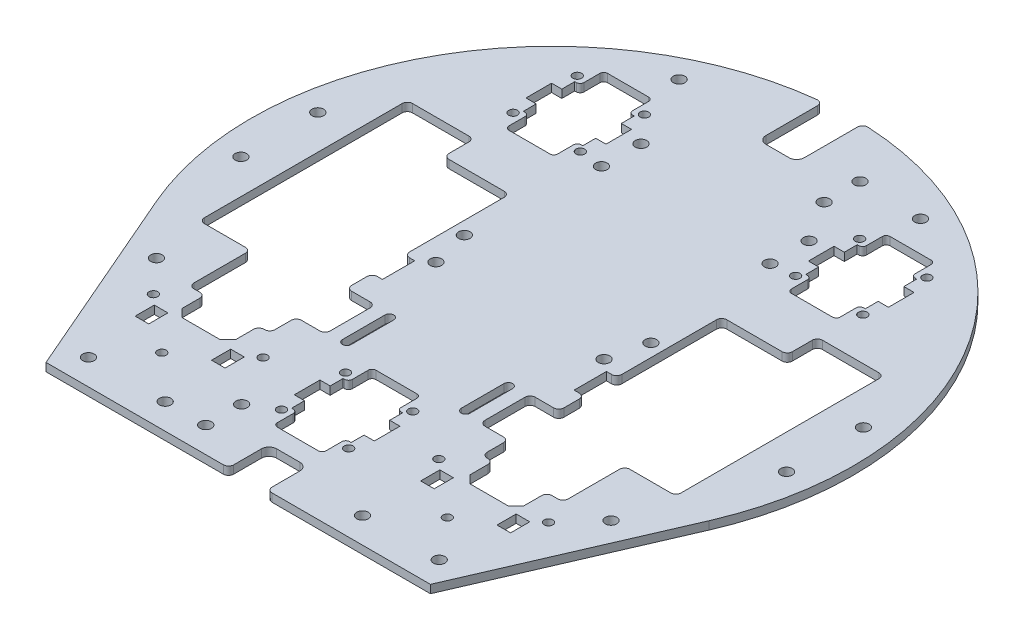
SolidWorks part; units mm, degrees
ref_plane "Front Plane" through (0, 0, 0) normal (0, 0, 1) x (1, 0, 0)
ref_plane "Top Plane" through (0, 0, 0) normal (0, 1, 0) x (1, 0, 0)
ref_plane "Right Plane" through (0, 0, 0) normal (1, 0, 0) x (0, 0, -1)
sketch "Sketch1" plane through (0, 0, 0) normal (0, 1, 0) x (1, 0, 0)
  circle A0 centre (0, 0) radius 117.5
  dimension "D1" = 235
extrude "Boss-Extrude1" add sketch "Sketch1" along normal blind 3.175
sketch "Sketch3" plane through (0, 0, 0) normal (0, 1, 0) x (1, 0, 0)
  line L3 (-107.8261, -46.6881) -> (-75, -122.5)
  line L5 (-75, -122.5) -> (75, -122.5)
  line L6 (75, -122.5) -> (107.8261, -46.6881)
  line L7 (107.8261, -46.6881) -> (-107.8261, -46.6881)
  line L8 (0, -122.5) -> (0, -117.5) construction
  circle A2 centre (0, 0) radius 117.5 construction
  dimension "D1" = 150
  dimension "D2" = 5
extrude "Boss-Extrude2" add sketch "Sketch3" along normal up to surface (3.175 mm away) up to face at (0, 3.175, 117.5)
sketch "Sketch4" plane through (0, 3.175, 0) normal (0, 1, 0) x (1, 0, 0)
  line L0 (70, 31.499) -> (70, -36.6986)
  line L1 (90, 31.499) -> (90, -36.6986)
  line L4 (93, 36.499) -> (67, 36.499)
  line L5 (90, -36.6986) -> (70, -36.6986) construction
  line L6 (67, 36.499) -> (67, 24.7405)
  line L7 (70, 31.499) -> (90, 31.499)
  line L8 (67, 24.7405) -> (41.4, 24.7405)
  line L9 (41.4, 24.7405) -> (41.4, -68.7747)
  line L10 (41.4, -68.7747) -> (73, -68.7747)
  line L11 (73, -68.7747) -> (73, -44.6986)
  line L12 (73, -44.6986) -> (93, -44.6986)
  line L13 (93, -44.6986) -> (93, 36.499)
  line L14 (46.4, 31.499) -> (89.2885, 31.499) construction
  line L15 (70, 31.499) -> (90, 31.499) construction
  line L19 (90, 31.499) -> (90, -36.6986) construction
  line L20 (70, 31.499) -> (70, -36.6986) construction
  line L22 (33.2, -41.8146) -> (33.2, -55.4255)
  line L24 (43.4, -41.8146) -> (33.2, -41.8146)
  line L25 (0, 0) -> (0, 30.6953) construction
  line L26 (-93, -44.6986) -> (-93, 36.499)
  line L27 (-73, -44.6986) -> (-93, -44.6986)
  line L28 (-73, -68.7747) -> (-73, -44.6986)
  line L29 (-41.4, -68.7747) -> (-73, -68.7747)
  line L30 (-41.4, 24.7405) -> (-41.4, -68.7747)
  line L31 (-67, 24.7405) -> (-41.4, 24.7405)
  line L32 (-67, 36.499) -> (-67, 24.7405)
  line L33 (-93, 36.499) -> (-67, 36.499)
  line L35 (33.2, -55.4255) -> (43.4, -55.4255) construction
  line L36 (39.4, -26.8239) -> (39.4, -18.2172)
  line L37 (39.4, -26.8239) -> (43.4, -26.8239)
  line L38 (43.4, -18.2172) -> (39.4, -18.2172)
  line L39 (68, 19.7405) -> (68, -67.7747)
  line L40 (68, -67.7747) -> (43.4, -67.7747)
  line L41 (43.4, 19.7405) -> (68, 19.7405)
  line L42 (43.4, 19.7405) -> (43.4, -18.2172)
  line L43 (43.4, -26.8239) -> (43.4, -41.8146)
  line L44 (43.4, -55.4255) -> (43.4, -67.7747)
  line L45 (43.4, -55.4255) -> (43.4, -67.7747) construction
  line L46 (43.4, -26.8239) -> (43.4, -41.8146) construction
  line L47 (43.4, 19.7405) -> (43.4, -18.2172) construction
  line L48 (43.4, 19.7405) -> (68, 19.7405) construction
  line L49 (68, -67.7747) -> (43.4, -67.7747) construction
  line L50 (68, 19.7405) -> (68, -67.7747) construction
  line L51 (43.4, -18.2172) -> (39.4, -18.2172) construction
  line L52 (39.4, -26.8239) -> (43.4, -26.8239) construction
  line L53 (39.4, -26.8239) -> (39.4, -18.2172) construction
  line L55 (43.4, -41.8146) -> (33.2, -41.8146) construction
  line L56 (33.2, -41.8146) -> (33.2, -55.4255) construction
  line L60 (33.2, -55.4255) -> (43.4, -55.4255)
  line L64 (90, -36.6986) -> (70, -36.6986)
  dimension "D1" = 2
  dimension "D2" = 5
  dimension "D3" = 5
  dimension "D4" = 8
  dimension "D5" = 3
  dimension "D6" = 5
  dimension "D7" = 5
  dimension "D8" = 3
  dimension "D9" = 2
extrude "Cut-Extrude1" cut sketch "Sketch4" against normal through all
sketch "Sketch8" plane through (0, 0, 0) normal (0, -1, 0) x (1, 0, 0)
  line L0 (-42, -78) -> (-68.225, -78) construction
  line L1 (13.1125, 12.5) -> (-13.1125, 12.5)
  line L2 (13.1125, 12.5) -> (13.1125, -12.5)
  line L3 (13.1125, -12.5) -> (-13.1125, -12.5)
  line L4 (-13.1125, 12.5) -> (-13.1125, -12.5)
  line L5 (13.1125, 12.5) -> (-13.1125, -12.5) construction
  line L6 (13.1125, -12.5) -> (-13.1125, 12.5) construction
  line L7 (-42, -53) -> (-42, -78) construction
  line L13 (0, 0) -> (0, -77.7063) construction
  line L14 (0, 80) -> (0, 0) construction
  line L15 (-42, -53) -> (-68.225, -53)
  line L16 (-42, -53) -> (-42, -78)
  line L17 (-42, -78) -> (-68.225, -78)
  line L18 (-68.225, -53) -> (-68.225, -78)
  line L19 (-42, -53) -> (-68.225, -78) construction
  line L20 (-42, -78) -> (-68.225, -53) construction
  line L21 (13.1125, 92.5) -> (-13.1125, 92.5)
  line L22 (13.1125, 92.5) -> (13.1125, 67.5)
  line L23 (13.1125, 67.5) -> (-13.1125, 67.5)
  line L24 (-13.1125, 92.5) -> (-13.1125, 67.5)
  line L25 (13.1125, 92.5) -> (-13.1125, 67.5) construction
  line L26 (13.1125, 67.5) -> (-13.1125, 92.5) construction
  line L27 (-42, -53) -> (-68.225, -53) construction
  line L28 (42, -78) -> (68.225, -78)
  line L29 (68.225, -53) -> (68.225, -78)
  line L30 (42, -78) -> (68.225, -53) construction
  line L31 (42, -53) -> (68.225, -78) construction
  line L32 (42, -53) -> (68.225, -53)
  line L33 (42, -53) -> (42, -78)
  point P0 (0, 0)
  point P15 (-55.1125, -65.5)
  point P20 (0, 80)
  point P29 (55.1125, -65.5)
  dimension "D1" = 42
  dimension "D2" = 80
hole_wizard "M3 Clearance Hole1" positions "Sketch9" profile "Sketch10" hole size "M3" standard "ANSI Metric" end condition through all
sketch "Sketch9" plane through (0, 3.175, 0) normal (0, 1, 0) x (1, 0, 0)
  point P0 (-68.225, 78)
  point P3 (-68.225, 53)
  point P6 (-42, 53)
  point P9 (-42, 78)
  point P12 (42, 78)
  point P15 (68.225, 78)
  point P18 (68.225, 53)
  point P21 (42, 53)
  point P24 (-13.1125, -67.5)
  point P27 (13.1125, -67.5)
  point P30 (13.1125, -92.5)
  point P33 (-13.1125, -92.5)
sketch "Sketch10" plane through (-68.225, 3.175, -78) normal (1, 0, 0) x (0, 0, 1)
  line L0 (0, 0) -> (0, 3.175)
  line L1 (0, 3.175) -> (1.7, 3.175)
  line L2 (1.7, 3.175) -> (1.7, 0)
  line L5 (1.7, 0) -> (0, 0)
  line L11 (0, -6.35) -> (0, 107.95) construction
  dimension "Thru Hole Dia." = 3.4
  dimension "Thru Hole Depth" = 3.175
sketch "Sketch11" plane through (0, 0, 0) normal (0, -1, 0) x (1, 0, 0)
  line L0 (47.6125, -48.2591) -> (62.6125, -48.2591)
  line L1 (62.6125, -82.7409) -> (47.6125, -82.7409)
  line L2 (62.6125, -82.7409) -> (47.6125, -82.7409)
  line L3 (47.6125, -48.2591) -> (62.6125, -48.2591)
  line L4 (-62.6125, -48.2591) -> (-47.6125, -48.2591)
  line L5 (-47.6125, -82.7409) -> (-62.6125, -82.7409)
  line L6 (-47.6125, -82.7409) -> (-62.6125, -82.7409)
  line L7 (-62.6125, -48.2591) -> (-47.6125, -48.2591)
  line L8 (-7.5, 97.2409) -> (7.5, 97.2409)
  line L9 (7.5, 62.7591) -> (-7.5, 62.7591)
  line L10 (7.5, 62.7591) -> (-7.5, 62.7591)
  line L11 (-7.5, 97.2409) -> (7.5, 97.2409)
sketch "Sketch12" plane through (0, 3.175, 0) normal (0, 1, 0) x (1, 0, 0)
  line L1 (-62.6125, 48.2591) -> (-47.6125, 48.2591) construction
  line L2 (-62.6125, 48.2591) -> (-62.6125, 82.7409) construction
  line L3 (-62.6125, 82.7409) -> (-47.6125, 82.7409) construction
  line L4 (-47.6125, 48.2591) -> (-47.6125, 82.7409) construction
  line L5 (47.6125, 48.2591) -> (62.6125, 48.2591) construction
  line L6 (47.6125, 48.2591) -> (47.6125, 82.7409) construction
  line L7 (47.6125, 82.7409) -> (62.6125, 82.7409) construction
  line L8 (62.6125, 48.2591) -> (62.6125, 82.7409) construction
  line L9 (-64.6125, 46.2591) -> (-45.6125, 46.2591)
  line L10 (-7.5, -97.2409) -> (7.5, -97.2409) construction
  line L11 (-7.5, -97.2409) -> (-7.5, -62.7591) construction
  line L12 (-7.5, -62.7591) -> (7.5, -62.7591) construction
  line L13 (7.5, -97.2409) -> (7.5, -62.7591) construction
  line L14 (-45.6125, 46.2591) -> (-45.6125, 84.7409)
  line L15 (-64.6125, 84.7409) -> (-45.6125, 84.7409)
  line L16 (-64.6125, 46.2591) -> (-64.6125, 84.7409)
  line L17 (45.6125, 46.2591) -> (64.6125, 46.2591)
  line L18 (64.6125, 46.2591) -> (64.6125, 84.7409)
  line L19 (45.6125, 84.7409) -> (64.6125, 84.7409)
  line L20 (45.6125, 46.2591) -> (45.6125, 84.7409)
  line L21 (-9.5, -99.2409) -> (9.5, -99.2409)
  line L22 (9.5, -99.2409) -> (9.5, -60.7591)
  line L23 (-9.5, -60.7591) -> (9.5, -60.7591)
  line L24 (-9.5, -99.2409) -> (-9.5, -60.7591)
  dimension "D1" = 2
extrude "Cut-Extrude3" cut sketch "Sketch12" against normal through all
sketch "Sketch13" plane through (0, 0, 0) normal (0, -1, 0) x (1, 0, 0)
  line L0 (-66.225, -75.0394) -> (-63.6125, -75.0394)
  line L1 (-63.6125, -55.9606) -> (-66.225, -55.9606)
  line L2 (-63.6125, -55.9606) -> (-66.225, -55.9606)
  line L3 (-66.225, -75.0394) -> (-63.6125, -75.0394)
  line L4 (-46.6125, -75.0394) -> (-44, -75.0394)
  line L5 (-44, -55.9606) -> (-46.6125, -55.9606)
  line L6 (-44, -55.9606) -> (-46.6125, -55.9606)
  line L7 (-46.6125, -75.0394) -> (-44, -75.0394)
  line L8 (63.6125, -75.0394) -> (66.225, -75.0394)
  line L9 (66.225, -55.9606) -> (63.6125, -55.9606)
  line L10 (66.225, -55.9606) -> (63.6125, -55.9606)
  line L11 (63.6125, -75.0394) -> (66.225, -75.0394)
  line L12 (44, -75.0394) -> (46.6125, -75.0394)
  line L13 (46.6125, -55.9606) -> (44, -55.9606)
  line L14 (46.6125, -55.9606) -> (44, -55.9606)
  line L15 (44, -75.0394) -> (46.6125, -75.0394)
  line L16 (8.5, 70.4606) -> (11.1125, 70.4606)
  line L17 (11.1125, 89.5394) -> (8.5, 89.5394)
  line L18 (11.1125, 89.5394) -> (8.5, 89.5394)
  line L19 (8.5, 70.4606) -> (11.1125, 70.4606)
  line L20 (-11.1125, 70.4606) -> (-8.5, 70.4606)
  line L21 (-8.5, 89.5394) -> (-11.1125, 89.5394)
  line L22 (-8.5, 89.5394) -> (-11.1125, 89.5394)
  line L23 (-11.1125, 70.4606) -> (-8.5, 70.4606)
sketch "Sketch14" plane through (0, 3.175, 0) normal (0, 1, 0) x (1, 0, 0)
  line L0 (-66.725, 55.4606) -> (-43.5, 55.4606)
  line L1 (-66.225, 55.9606) -> (-44, 55.9606) construction
  line L2 (-66.225, 55.9606) -> (-66.225, 75.0394) construction
  line L3 (-66.225, 75.0394) -> (-44, 75.0394) construction
  line L4 (-44, 55.9606) -> (-44, 75.0394) construction
  line L5 (44, 55.9606) -> (66.225, 55.9606) construction
  line L6 (44, 55.9606) -> (44, 75.0394) construction
  line L7 (44, 75.0394) -> (66.225, 75.0394) construction
  line L8 (66.225, 55.9606) -> (66.225, 75.0394) construction
  line L9 (-11.1125, -89.5394) -> (11.1125, -89.5394) construction
  line L10 (-11.1125, -89.5394) -> (-11.1125, -70.4606) construction
  line L11 (-11.1125, -70.4606) -> (11.1125, -70.4606) construction
  line L12 (11.1125, -89.5394) -> (11.1125, -70.4606) construction
  line L13 (-43.5, 55.4606) -> (-43.5, 75.5394)
  line L14 (-66.725, 75.5394) -> (-43.5, 75.5394)
  line L15 (-66.725, 55.4606) -> (-66.725, 75.5394)
  line L16 (43.5, 55.4606) -> (66.725, 55.4606)
  line L17 (66.725, 55.4606) -> (66.725, 75.5394)
  line L18 (43.5, 75.5394) -> (66.725, 75.5394)
  line L19 (43.5, 55.4606) -> (43.5, 75.5394)
  line L20 (-11.6125, -90.0394) -> (11.6125, -90.0394)
  line L21 (11.6125, -90.0394) -> (11.6125, -69.9606)
  line L22 (-11.6125, -69.9606) -> (11.6125, -69.9606)
  line L23 (-11.6125, -90.0394) -> (-11.6125, -69.9606)
  dimension "D1" = 0.5
extrude "Cut-Extrude4" cut sketch "Sketch14" against normal through all
sketch "Sketch15" plane through (0, 3.175, 0) normal (0, 1, 0) x (1, 0, 0)
  line L0 (-66.725, 75.5394) -> (-66.725, 55.4606) construction
  line L1 (-70.725, 60.5) -> (-39.5, 60.5)
  line L2 (-70.725, 60.5) -> (-70.725, 70.5)
  line L3 (-70.725, 70.5) -> (-39.5, 70.5)
  line L4 (-39.5, 60.5) -> (-39.5, 70.5)
  line L5 (-70.725, 60.5) -> (-39.5, 70.5) construction
  line L6 (-70.725, 70.5) -> (-39.5, 60.5) construction
  line L7 (39.5, 60.5) -> (70.725, 60.5)
  line L8 (39.5, 60.5) -> (39.5, 70.5)
  line L9 (39.5, 70.5) -> (70.725, 70.5)
  line L10 (70.725, 60.5) -> (70.725, 70.5)
  line L11 (39.5, 60.5) -> (70.725, 70.5) construction
  line L12 (39.5, 70.5) -> (70.725, 60.5) construction
  line L13 (-15.6125, -85) -> (15.6125, -85)
  line L14 (-15.6125, -85) -> (-15.6125, -75)
  line L15 (-15.6125, -75) -> (15.6125, -75)
  line L16 (15.6125, -85) -> (15.6125, -75)
  line L17 (-15.6125, -85) -> (15.6125, -75) construction
  line L18 (-15.6125, -75) -> (15.6125, -85) construction
  point P0 (-55.1125, 65.5)
  point P5 (55.1125, 65.5)
  point P11 (0, -80)
  dimension "D1" = 4
  dimension "D2" = 10
extrude "Cut-Extrude5" cut sketch "Sketch15" against normal through all
sketch "Sketch16" plane through (0, 0, 0) normal (0, -1, 0) x (1, 0, 0)
  line L4 (-5.225, -101.6482) -> (-2.225, -101.6482) construction
  line L5 (-2.225, -97.6482) -> (-5.225, -97.6482) construction
  line L6 (2.225, 112.6982) -> (5.225, 112.6982) construction
  line L7 (5.225, 116.6982) -> (2.225, 116.6982) construction
  line L8 (-3.775, 122.5) -> (-3.775, 109.6982)
  line L9 (-75, 122.5) -> (75, 122.5) construction
  line L10 (-0.775, 106.6982) -> (8.225, 106.6982)
  line L11 (11.225, 109.6982) -> (11.225, 122.5)
  line L12 (11.225, 122.5) -> (-3.775, 122.5)
  line L13 (3.725, 122.5) -> (3.725, 106.6982) construction
  line L14 (2.225, 114.6982) -> (5.225, 114.6982) construction
  line L15 (-11.225, -116.9626) -> (-11.225, -94.6482)
  line L16 (-8.225, -91.6482) -> (0.775, -91.6482)
  line L17 (3.775, -94.6482) -> (3.775, -117.4393)
  line L18 (-11.225, -94.6482) -> (3.775, -94.6482) construction
  line L19 (-3.725, -91.6482) -> (-3.725, -99.6482) construction
  line L20 (-2.225, -99.6482) -> (-5.225, -99.6482) construction
  arc A4 (-5.225, -97.6482) -> (-5.225, -101.6482) centre (-5.225, -99.6482) ccw construction
  arc A5 (-2.225, -101.6482) -> (-2.225, -97.6482) centre (-2.225, -99.6482) ccw construction
  arc A6 (5.225, 112.6982) -> (5.225, 116.6982) centre (5.225, 114.6982) ccw construction
  arc A7 (2.225, 116.6982) -> (2.225, 112.6982) centre (2.225, 114.6982) ccw construction
  arc A8 (-3.775, 109.6982) -> (-0.775, 106.6982) centre (-0.775, 109.6982) ccw
  arc A9 (8.225, 106.6982) -> (11.225, 109.6982) centre (8.225, 109.6982) ccw
  arc A10 (-107.8261, 46.6881) -> (107.8261, 46.6881) centre (0, 0) ccw construction
  arc A11 (-11.225, -94.6482) -> (-8.225, -91.6482) centre (-8.225, -94.6482) cw
  arc A12 (0.775, -91.6482) -> (3.775, -94.6482) centre (0.775, -94.6482) cw
  arc A13 (-11.225, -116.9626) -> (3.775, -117.4393) centre (0, 0) ccw
  point P26 (3.725, 114.6982)
  point P37 (-3.725, -99.6482)
  dimension "D1" = 8
  dimension "D3" = 3
  dimension "D4" = 8
  dimension "D2" = 15
extrude "Cut-Extrude6" cut sketch "Sketch16" against normal through all
fillet "Fillet1" radius 2 4 edges at (3.775, 1.5875, -117.4393) (-11.225, 1.5875, -116.9626) (11.225, 1.5875, 122.5) (-3.775, 1.5875, 122.5)
hole_wizard "#8 Clearance Hole1" positions "Sketch17" profile "Sketch18" hole size "#8" standard "ANSI Inch" end condition through all
sketch "Sketch17" plane through (0, 0, 0) normal (0, 1, 0) x (1, 0, 0)
  circle A0 centre (-88.6902, -65.7156) radius 1.7272 construction
  circle A1 centre (-106.4483, -15) radius 1.7272 construction
  circle A2 centre (-106.4483, 15) radius 1.7272 construction
  circle A3 centre (32.8, 67.45) radius 1.7272 construction
  circle A4 centre (32.9, 52.1319) radius 1.7272 construction
  circle A5 centre (36.4, 2.1319) radius 1.7272 construction
  circle A6 centre (32.8, -12.55) radius 1.7272 construction
  circle A7 centre (-32.8, -12.55) radius 1.7272 construction
  circle A8 centre (-36.4, 2.1319) radius 1.7272 construction
  circle A9 centre (-32.9, 52.1319) radius 1.7272 construction
  circle A10 centre (-32.8, 67.45) radius 1.7272 construction
  circle A11 centre (-47.0917, 96.6365) radius 1.7272 construction
  circle A12 centre (47.0917, 96.6365) radius 1.7272 construction
  circle A13 centre (106.4483, 15) radius 1.7272 construction
  circle A14 centre (106.4483, -15) radius 1.7272 construction
  circle A15 centre (88.6902, -65.7156) radius 1.7272 construction
  circle A16 centre (38.5, -112.5) radius 1.7272 construction
  circle A19 centre (-38.5, -112.5) radius 1.7272 construction
  circle A20 centre (-68.4328, -112.5) radius 1.7272 construction
  circle A21 centre (-88.6902, -65.7156) radius 1.7272
  circle A22 centre (-106.4483, -15) radius 1.7272
  circle A23 centre (-106.4483, 15) radius 1.7272
  circle A24 centre (32.8, 67.45) radius 1.7272
  circle A25 centre (32.9, 52.1319) radius 1.7272
  circle A26 centre (36.4, 2.1319) radius 1.7272
  circle A27 centre (32.8, -12.55) radius 1.7272
  circle A28 centre (-32.8, -12.55) radius 1.7272
  circle A29 centre (-36.4, 2.1319) radius 1.7272
  circle A30 centre (-32.9, 52.1319) radius 1.7272
  circle A31 centre (-32.8, 67.45) radius 1.7272
  circle A32 centre (-47.0917, 96.6365) radius 1.7272
  circle A33 centre (47.0917, 96.6365) radius 1.7272
  circle A34 centre (106.4483, 15) radius 1.7272
  circle A35 centre (106.4483, -15) radius 1.7272
  circle A36 centre (88.6902, -65.7156) radius 1.7272
  circle A37 centre (38.5, -112.5) radius 1.7272
  circle A38 centre (-22.6638, -98.5) radius 1.7272
  circle A39 centre (-22.6638, -112.5) radius 1.7272
  circle A40 centre (-38.5, -112.5) radius 1.7272
  circle A41 centre (-68.4328, -112.5) radius 1.7272
  circle A42 centre (68.4328, -112.5) radius 1.7272 construction
  circle A43 centre (68.4328, -112.5) radius 1.7272
  circle A45 centre (22.6638, 83.45) radius 1.7272
  circle A47 centre (22.6638, 97.45) radius 1.7272
  circle A48 centre (22.6638, 83.45) radius 1.7272 construction
  circle A50 centre (-22.6638, -98.5) radius 1.7272 construction
  circle A51 centre (-22.6638, -112.5) radius 1.7272 construction
  circle A52 centre (22.6638, 97.45) radius 1.7272 construction
  point P1 (-88.6902, -65.7156)
  point P3 (-106.4483, -15)
  point P5 (-106.4483, 15)
  point P7 (32.8, 67.45)
  point P9 (32.9, 52.1319)
  point P11 (36.4, 2.1319)
  point P13 (32.8, -12.55)
  point P15 (-32.8, -12.55)
  point P17 (-36.4, 2.1319)
  point P19 (-32.9, 52.1319)
  point P21 (-32.8, 67.45)
  point P23 (-47.0917, 96.6365)
  point P25 (47.0917, 96.6365)
  point P27 (106.4483, 15)
  point P29 (106.4483, -15)
  point P31 (88.6902, -65.7156)
  point P33 (38.5, -112.5)
  point P35 (-22.6638, -98.5)
  point P37 (-22.6638, -112.5)
  point P39 (-38.5, -112.5)
  point P41 (-68.4328, -112.5)
  point P109 (68.4328, -112.5)
  point P116 (22.6638, 83.45)
  point P119 (22.6638, 97.45)
sketch "Sketch18" plane through (-88.6902, 0, 65.7156) normal (1, 0, 0) x (0, 0, -1)
  line L0 (0, 0) -> (0, 3.175)
  line L1 (0, 3.175) -> (2.2479, 3.175)
  line L2 (2.2479, 3.175) -> (2.2479, 0)
  line L5 (2.2479, 0) -> (0, 0)
  line L11 (0, -6.35) -> (0, 107.95) construction
  dimension "Thru Hole Dia." = 4.4958
  dimension "Thru Hole Depth" = 3.175
hole_wizard "M3 Clearance Hole2" positions "Sketch19" profile "Sketch20" hole size "M3" standard "ANSI Metric" end condition through all
sketch "Sketch19" plane through (0, 0, 0) normal (0, -1, 0) x (-1, 0, 0)
  circle A1 centre (77.1, -78.5087) radius 1.8
  circle A2 centre (-77.1, -78.5087) radius 1.8 construction
  circle A3 centre (-55.7, -96.6207) radius 1.8 construction
  circle A4 centre (-34.3, -78.5087) radius 1.8 construction
  circle A7 centre (-77.1, -78.5087) radius 1.8
  circle A8 centre (-55.7, -96.6207) radius 1.8
  circle A9 centre (-34.3, -78.5087) radius 1.8
  circle A10 centre (34.3, -78.5087) radius 1.8
  circle A11 centre (55.7, -96.6207) radius 1.8
  circle A12 centre (55.7, -96.6207) radius 1.8 construction
  circle A13 centre (77.1, -78.5087) radius 1.8 construction
  circle A14 centre (34.3, -78.5087) radius 1.8 construction
  point P1 (77.1, -78.5087)
  point P4 (-77.1, -78.5087)
  point P6 (-55.7, -96.6207)
  point P8 (-34.3, -78.5087)
  point P10 (34.3, -78.5087)
  point P12 (55.7, -96.6207)
sketch "Sketch20" plane through (-77.1, 0, 78.5087) normal (1, 0, 0) x (0, 0, -1)
  line L0 (0, 0) -> (0, 3.175)
  line L1 (0, 3.175) -> (1.7, 3.175)
  line L2 (1.7, 3.175) -> (1.7, 0)
  line L5 (1.7, 0) -> (0, 0)
  line L11 (0, -6.35) -> (0, 107.95) construction
  dimension "Thru Hole Dia." = 3.4
  dimension "Thru Hole Depth" = 3.175
sketch "Sketch22" plane through (0, 0, 0) normal (0, -1, 0) x (1, 0, 0)
  line L11 (64.7, 72.5637) -> (64.7, 76.0717) construction
  line L12 (55.319, 78.8177) -> (50.7, 78.8177) construction
  line L13 (47.7, 76.7927) -> (47.7, 71.8427) construction
  line L14 (64.7, 72.5637) -> (64.7, 76.0717) construction
  line L15 (55.319, 78.8177) -> (50.7, 78.8177) construction
  line L16 (47.7, 76.7927) -> (47.7, 71.8427) construction
  line L17 (41.4, 68.7747) -> (73, 68.7747) construction
  line L18 (47.7, 68.7747) -> (64.7, 68.7747) construction
  line L19 (47.7, 68.7747) -> (47.7, 78.8177) construction
  line L20 (47.7, 78.8177) -> (64.7, 78.8177) construction
  line L21 (64.7, 68.7747) -> (64.7, 78.8177) construction
  line L22 (45.7, 66.7747) -> (45.7, 77.8177)
  line L23 (48.7, 80.8177) -> (63.7, 80.8177)
  line L24 (66.7, 66.7747) -> (66.7, 77.8177)
  line L25 (45.7, 66.7747) -> (66.7, 66.7747)
  line L26 (45.7, 77.8177) -> (48.7, 80.8177)
  line L27 (63.7, 80.8177) -> (66.7, 77.8177)
  line L28 (45.7, 66.7747) -> (45.7, 80.8177) construction
  line L29 (45.7, 80.8177) -> (66.7, 80.8177) construction
  line L30 (66.7, 66.7747) -> (66.7, 80.8177) construction
  line L31 (45.7, 77.8177) -> (45.7, 80.8177) construction
  line L32 (45.7, 80.8177) -> (48.7, 80.8177) construction
  line L33 (66.7, 77.8177) -> (66.7, 80.8177) construction
  line L34 (66.7, 80.8177) -> (63.7, 80.8177) construction
  line L35 (0, 0) -> (0, 34.6023) construction
  line L36 (-45.7, 66.7747) -> (-66.7, 66.7747)
  line L37 (-45.7, 66.7747) -> (-45.7, 77.8177)
  line L38 (-45.7, 77.8177) -> (-48.7, 80.8177)
  line L39 (-48.7, 80.8177) -> (-63.7, 80.8177)
  line L40 (-63.7, 80.8177) -> (-66.7, 77.8177)
  line L41 (-66.7, 66.7747) -> (-66.7, 77.8177)
  dimension "D1" = 2
  dimension "D2" = 3
extrude "Cut-Extrude8" cut sketch "Sketch22" against normal through all
fillet "Fillet4" radius 1.5 24 edges at (45.6125, 1.5875, -75.5394) (64.6125, 1.5875, -75.5394) (64.6125, 1.5875, -55.4606) (45.6125, 1.5875, -55.4606) (64.6125, 1.5875, -46.2591) (64.6125, 1.5875, -84.7409) (45.6125, 1.5875, -84.7409) (45.6125, 1.5875, -46.2591) (-64.6125, 1.5875, -46.2591) (-45.6125, 1.5875, -46.2591) (-45.6125, 1.5875, -84.7409) (-64.6125, 1.5875, -84.7409) (-64.6125, 1.5875, -75.5394) (-64.6125, 1.5875, -55.4606) (-45.6125, 1.5875, -55.4606) (-45.6125, 1.5875, -75.5394) (-9.5, 1.5875, 69.9606) (-9.5, 1.5875, 60.7591) (9.5, 1.5875, 60.7591) (9.5, 1.5875, 69.9606) (9.5, 1.5875, 90.0394) (-9.5, 1.5875, 99.2409) (9.5, 1.5875, 99.2409) (-9.5, 1.5875, 90.0394)
sketch "Sketch29" plane through (0, 3.175, 0) normal (0, 1, 0) x (1, 0, 0)
  line L14 (43.4, -28.8239) -> (43.4, -16.2172)
  line L17 (37.4, -28.8239) -> (43.4, -28.8239)
  line L18 (37.4, -16.2172) -> (37.4, -28.8239)
  line L19 (43.4, -16.2172) -> (37.4, -16.2172)
  line L20 (37.4, -28.8239) -> (43.4, -28.8239)
  line L21 (37.4, -16.2172) -> (37.4, -28.8239)
  line L22 (43.4, -16.2172) -> (37.4, -16.2172)
  line L28 (0, 0) -> (0, -34.7576) construction
  line L40 (-37.4, -16.2172) -> (-37.4, -28.8239)
  line L41 (-43.4, -16.2172) -> (-37.4, -16.2172)
  line L42 (-43.4, -28.8239) -> (-43.4, -16.2172)
  line L43 (-37.4, -28.8239) -> (-43.4, -28.8239)
  line L47 (43.4, -38.8146) -> (43.4, -58.4255)
  line L48 (-43.4, -38.8146) -> (-30.2, -38.8146)
  line L49 (-30.2, -38.8146) -> (-30.2, -58.4255)
  line L50 (30.2, -58.4255) -> (43.4, -58.4255)
  line L51 (30.2, -38.8146) -> (30.2, -58.4255)
  line L52 (43.4, -38.8146) -> (30.2, -38.8146)
  line L53 (30.2, -58.4255) -> (43.4, -58.4255)
  line L54 (30.2, -38.8146) -> (30.2, -58.4255)
  line L55 (43.4, -38.8146) -> (30.2, -38.8146)
  line L56 (-30.2, -58.4255) -> (-43.4, -58.4255)
  line L57 (-43.4, -38.8146) -> (-43.4, -58.4255)
  dimension "D2" = 3
  dimension "D1" = 2
extrude "Cut-Extrude9" cut sketch "Sketch29" against normal through all
fillet "Fillet5" radius 2 16 edges at (30.2, 1.5875, 38.8146) (30.2, 1.5875, 58.4255) (41.4, 1.5875, 58.4255) (41.4, 1.5875, 38.8146) (41.4, 1.5875, 28.8239) (41.4, 1.5875, 16.2172) (41.4, 1.5875, -24.7405) (67, 1.5875, -24.7405) (67, 1.5875, -36.499) (93, 1.5875, -36.499) (93, 1.5875, 44.6986) (73, 1.5875, 44.6986) (73, 1.5875, 68.7747) (66.7, 1.5875, 68.7747) (41.4, 1.5875, 68.7747) (45.7, 1.5875, 68.7747)
fillet "Fillet6" radius 2 16 edges at (-41.4, 1.5875, 28.8239) (-41.4, 1.5875, 38.8146) (-30.2, 1.5875, 38.8146) (-30.2, 1.5875, 58.4255) (-41.4, 1.5875, 58.4255) (-73, 1.5875, 68.7747) (-73, 1.5875, 44.6986) (-93, 1.5875, 44.6986) (-67, 1.5875, -36.499) (-67, 1.5875, -24.7405) (-41.4, 1.5875, -24.7405) (-41.4, 1.5875, 16.2172) (-93, 1.5875, -36.499) (-45.7, 1.5875, 68.7747) (-41.4, 1.5875, 68.7747) (-66.7, 1.5875, 68.7747)
sketch "Sketch30" plane through (0, 0, 0) normal (0, -1, 0) x (1, 0, 0)
  line L0 (-73.1, 89.3177) -> (-73.1, 82.1333) construction
  line L1 (-73.1, 82.1333) -> (-68.1, 82.1333) construction
  line L2 (-68.1, 82.1333) -> (-68.1, 89.3177) construction
  line L3 (-68.1, 89.3177) -> (-73.1, 89.3177) construction
  line L4 (-38.3, 82.1333) -> (-38.3, 89.3177) construction
  line L5 (-38.3, 89.3177) -> (-43.3, 89.3177) construction
  line L6 (-43.3, 89.3177) -> (-43.3, 82.1333) construction
  line L7 (-43.3, 82.1333) -> (-38.3, 82.1333) construction
  line L8 (38.3, 89.3177) -> (38.3, 82.1333) construction
  line L9 (38.3, 82.1333) -> (43.3, 82.1333) construction
  line L10 (43.3, 82.1333) -> (43.3, 89.3177) construction
  line L11 (43.3, 89.3177) -> (38.3, 89.3177) construction
  line L12 (73.1, 82.1333) -> (73.1, 89.3177) construction
  line L13 (73.1, 89.3177) -> (68.1, 89.3177) construction
  line L14 (68.1, 89.3177) -> (68.1, 82.1333) construction
  line L15 (68.1, 82.1333) -> (73.1, 82.1333) construction
  line L16 (-73.1, 89.3177) -> (-73.1, 82.1333) construction
  line L17 (-73.1, 82.1333) -> (-68.1, 82.1333) construction
  line L18 (-68.1, 82.1333) -> (-68.1, 89.3177) construction
  line L19 (-68.1, 89.3177) -> (-73.1, 89.3177) construction
  line L20 (-38.3, 82.1333) -> (-38.3, 89.3177) construction
  line L21 (-38.3, 89.3177) -> (-43.3, 89.3177) construction
  line L22 (-43.3, 89.3177) -> (-43.3, 82.1333) construction
  line L23 (-43.3, 82.1333) -> (-38.3, 82.1333) construction
  line L24 (38.3, 89.3177) -> (38.3, 82.1333) construction
  line L25 (38.3, 82.1333) -> (43.3, 82.1333) construction
  line L26 (43.3, 82.1333) -> (43.3, 89.3177) construction
  line L27 (43.3, 89.3177) -> (38.3, 89.3177) construction
  line L28 (73.1, 82.1333) -> (73.1, 89.3177) construction
  line L29 (73.1, 89.3177) -> (68.1, 89.3177) construction
  line L30 (68.1, 89.3177) -> (68.1, 82.1333) construction
  line L31 (68.1, 82.1333) -> (73.1, 82.1333) construction
  line L32 (-73.25, 89.4677) -> (-73.25, 81.9833)
  line L33 (-73.25, 81.9833) -> (-67.95, 81.9833)
  line L34 (-67.95, 81.9833) -> (-67.95, 89.4677)
  line L35 (-67.95, 89.4677) -> (-73.25, 89.4677)
  line L36 (-38.15, 81.9833) -> (-38.15, 89.4677)
  line L37 (-38.15, 89.4677) -> (-43.45, 89.4677)
  line L38 (-43.45, 89.4677) -> (-43.45, 81.9833)
  line L39 (-43.45, 81.9833) -> (-38.15, 81.9833)
  line L40 (38.15, 89.4677) -> (38.15, 81.9833)
  line L41 (38.15, 81.9833) -> (43.45, 81.9833)
  line L42 (43.45, 81.9833) -> (43.45, 89.4677)
  line L43 (43.45, 89.4677) -> (38.15, 89.4677)
  line L44 (73.25, 81.9833) -> (73.25, 89.4677)
  line L45 (73.25, 89.4677) -> (67.95, 89.4677)
  line L46 (67.95, 89.4677) -> (67.95, 81.9833)
  line L47 (67.95, 81.9833) -> (73.25, 81.9833)
  dimension "D1" = 0.15
extrude "Cut-Extrude10" cut sketch "Sketch30" against normal through all
hole_wizard "M3 Clearance Slot1" positions "Sketch26" profile "Sketch24" size "M3" standard "ANSI Metric" slot yes end condition through all
sketch "Sketch26" plane through (0, 3.175, 0) normal (0, 1, 0) x (1, 0, 0)
  line L0 (23.2, -58.62) -> (23.2, -38.62) construction
  line L8 (23.2, -48.62) -> (30.2, -48.62)
  line L10 (30.2, -40.8146) -> (30.2, -56.4255) construction
  line L11 (0, 0) -> (0, -34.2526) construction
  point P0 (23.2, -48.62)
  point P35 (-23.2, -48.62)
  dimension "D1" = 20
  dimension "D2" = 7
sketch "Sketch24" plane through (23.2, 3.175, 48.62) normal (1, 0, 0) x (0, 0, 1)
  line L0 (0, 0) -> (0, 3.175)
  line L1 (0, 3.175) -> (1.7, 3.175)
  line L2 (1.7, 3.175) -> (1.7, 0)
  line L5 (1.7, 0) -> (0, 0)
  line L11 (0, -6.35) -> (0, 107.95) construction
  dimension "Thru Hole Dia." = 3.4
  dimension "Thru Hole Depth" = 3.175
